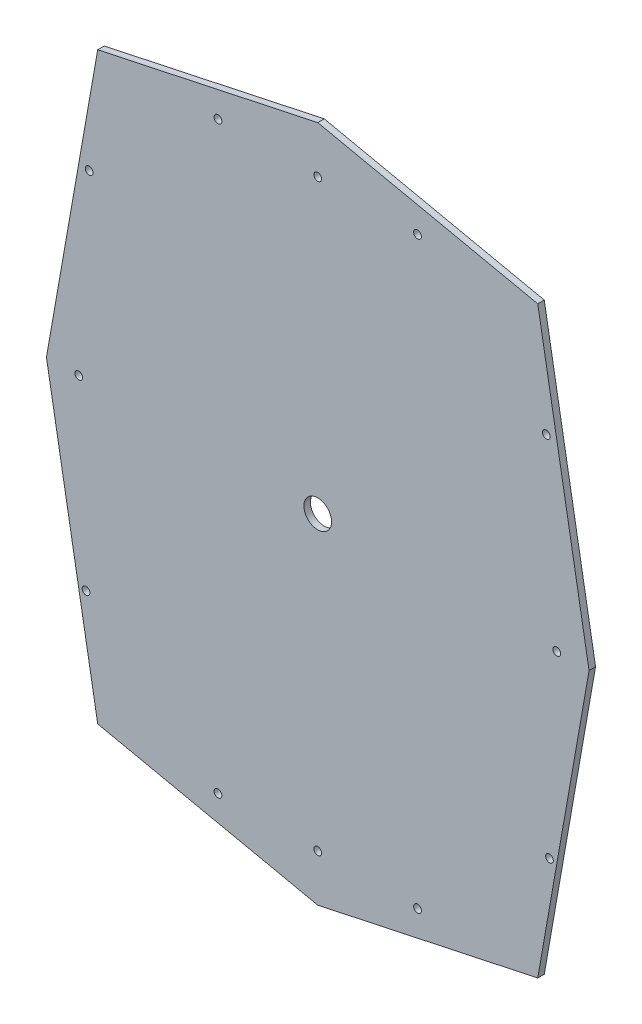
SolidWorks part; units mm, degrees
ref_plane "Front Plane" through (0, 0, 0) normal (0, 0, 1) x (1, 0, 0)
ref_plane "Top Plane" through (0, 0, 0) normal (0, 1, 0) x (1, 0, 0)
ref_plane "Right Plane" through (0, 0, 0) normal (1, 0, 0) x (0, 0, -1)
sketch "Sketch1" plane through (0, 0, 0) normal (0, 0, 1) x (1, 0, 0)
  line L0 (-107.5, 142.6399) -> (-132.5632, 0)
  line L6 (0, 188.5) -> (0, 0) construction
  line L7 (55, 0) -> (-55, 0) construction
  line L10 (-107.5, -142.6399) -> (-132.5632, 0)
  line L12 (0, -55) -> (0, 55) construction
  line L13 (0, 188.5) -> (0, 142.6399) construction
  line L14 (-130, 89.4108) -> (-111.25, 89.4108) construction
  line L15 (-141, 0) -> (-116.7559, 0) construction
  line L18 (107.5, -142.6399) -> (132.5632, 0)
  line L19 (107.5, 142.6399) -> (132.5632, 0)
  line L24 (-107.5, 142.6399) -> (0, 165.5699)
  line L25 (0, 165.5699) -> (107.5, 142.6399)
  line L27 (-184.8413, 0) -> (193.3832, 0) construction
  line L33 (0, -165.5699) -> (107.5, -142.6399)
  line L34 (-107.5, -142.6399) -> (0, -165.5699)
  circle A0 centre (0, 0) radius 6.7659
  circle A16 centre (48.75, -142.6399) radius 1.8987 construction
  circle A17 centre (0, -142.6399) radius 1.8987 construction
  circle A18 centre (-48.75, -142.6399) radius 1.8987 construction
  circle A19 centre (-113.2269, -89.1534) radius 1.8987 construction
  circle A20 centre (-116.75, 0.1657) radius 1.8987 construction
  circle A21 centre (-111.6902, 89.4108) radius 1.8987 construction
  circle A25 centre (48.75, -142.6399) radius 1.8987
  circle A26 centre (0, -142.6399) radius 1.8987
  circle A27 centre (-48.75, -142.6399) radius 1.8987
  circle A28 centre (-113.2269, -89.1534) radius 1.8987
  circle A29 centre (-116.75, 0.1657) radius 1.8987
  circle A30 centre (-111.6902, 89.4108) radius 1.8987
  circle A31 centre (111.6902, 89.4108) radius 1.8987
  circle A32 centre (116.75, 0.1657) radius 1.8986
  circle A33 centre (113.2269, -89.1534) radius 1.8692
  circle A34 centre (48.75, 142.6399) radius 1.8987 construction
  circle A35 centre (0, 142.6399) radius 1.8987 construction
  circle A36 centre (-48.75, 142.6399) radius 1.8987 construction
  circle A37 centre (48.75, 142.6399) radius 1.8987
  circle A38 centre (0, 142.6399) radius 1.8987
  circle A39 centre (-48.75, 142.6399) radius 1.8987
  point P0 (0, 0)
  point P16 (0, -142.6399)
  point P17 (0, 142.6399)
  dimension "D1" = 13.5319
extrude "MainBody" add sketch "Sketch1" along normal blind 3.175
